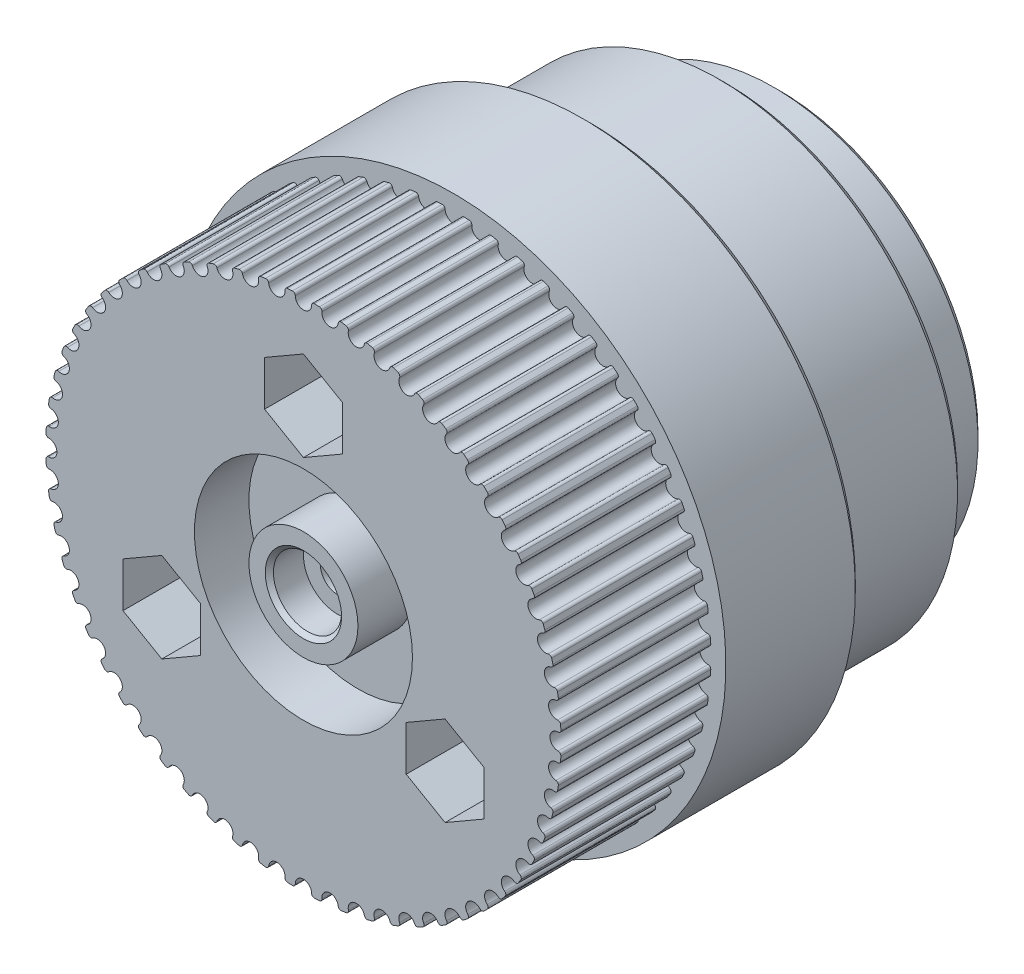
SolidWorks part; units mm, degrees
ref_plane "Front Plane" through (0, 0, 0) normal (0, 0, 1) x (1, 0, 0)
ref_plane "Top Plane" through (0, 0, 0) normal (0, 1, 0) x (1, 0, 0)
ref_plane "Right Plane" through (0, 0, 0) normal (1, 0, 0) x (0, 0, -1)
ref_axis "Axis1" through (0, 0, 55) along (0, 0, -1)
sketch "SketchRevolveGearBelt02" plane through (0, 0, 0) normal (1, 0, 0) x (0, 0, -1)
  line L0 (0, 0) -> (1, 0) construction
  line L1 (11, 0) -> (11, 18.9081)
  line L2 (11, 18.9081) -> (0, 18.9081)
  line L3 (0, 18.9081) -> (0, 0)
  line L4 (0, 0) -> (11, 0)
  dimension "GearBeltSide1" = 11
  dimension "GearBeltOutsideDiameter" = 18.9081
revolve "GearBelt02" add sketch "SketchRevolveGearBelt02" angle 360 about L0
sketch "SketchToothGearBelt02" plane through (0, 0, 0) normal (0, 0, 1) x (1, 0, 0)
  line L0 (-0.8105, 18.8907) -> (0, 21.4481)
  line L1 (0, 21.4481) -> (0.8105, 18.8907)
  arc A0 (0.8105, 18.8907) -> (0.6, 18.6891) centre (0.8018, 18.6891) ccw
  arc A1 (0.6, 18.6891) -> (-0.6, 18.6891) centre (0, 18.6891) cw
  arc A2 (-0.6, 18.6891) -> (-0.8105, 18.8907) centre (-0.8018, 18.6891) ccw
  dimension "GearBeltToothR1" = 0.4036
  dimension "GearBeltToothR2" = 1.2
  dimension "GearBeltToothCapX1" = 0.8105
  dimension "GearBeltToothCapY1" = 2.5574
  dimension "GearBeltToothCapX2" = 0.8105
  dimension "GearBeltToothCapY2" = 2.5574
extrude "ToothExtrudeCutGearBelt02" cut sketch "SketchToothGearBelt02" against normal blind 11
pattern_circular "PatternGearBelt02" count 60 every 6 about axis through (0, 0, 55) along (0, 0, -1) of "ToothExtrudeCutGearBelt02"
sketch "Эскиз2" plane through (0, 0, -11) normal (0, 0, -1) x (-1, 0, 0)
  circle A0 centre (0, 0) radius 20
extrude "Бобышка-Вытянуть1" add sketch "Эскиз2" along normal blind 10
sketch "Эскиз3" plane through (0, 0, -21) normal (0, 0, -1) x (-1, 0, 0)
  circle A0 centre (0, 0) radius 17.5
extrude "Бобышка-Вытянуть2" add sketch "Эскиз3" along normal blind 10
sketch "Эскиз4" plane through (0, 0, -31) normal (0, 0, -1) x (-1, 0, 0)
  circle A0 centre (0, 0) radius 15
extrude "Бобышка-Вытянуть3" add sketch "Эскиз4" along normal blind 4
sketch "Эскиз5" plane through (0, 0, 0) normal (0, 0, 1) x (1, 0, 0)
  circle A0 centre (0, 0) radius 12 construction
  circle A1 centre (0, 12) radius 1.75
  circle A2 centre (10.3923, -6) radius 1.75
  circle A3 centre (-10.3923, -6) radius 1.75
  point P12 (0, 0)
  dimension "D1" = 3.5
  dimension "D2" = 24
  dimension "D3" = 3
extrude "Вырез-Вытянуть1" cut sketch "Эскиз5" against normal through all
sketch "Эскиз6" plane through (0, 0, 0) normal (0, 0, 1) x (1, 0, 0)
  line L1 (0, 8.7091) -> (2.85, 10.3546)
  line L2 (2.85, 10.3546) -> (2.85, 13.6454)
  line L3 (2.85, 13.6454) -> (0, 15.2909)
  line L4 (0, 15.2909) -> (-2.85, 13.6454)
  line L5 (-2.85, 13.6454) -> (-2.85, 10.3546)
  line L6 (-2.85, 10.3546) -> (0, 8.7091)
  circle A0 centre (0, 12) radius 2.85 construction
  dimension "D1" = 5.7
extrude "Вырез-Вытянуть2" cut sketch "Эскиз6" against normal blind 20
pattern_circular "Круговой массив1" count 3 over 360 about axis through (0, 0, -21) along (0, 0, 1) of "Вырез-Вытянуть2" reverse direction yes
chamfer "Chamfer1" distance 0.5 angle 45 3 edges at (-20, 0, -21) (-15, 0, -35) (-17.5, 0, -31)
sketch "Эскиз7" plane through (0, 0, 0) normal (0, 0, 1) x (1, 0, 0)
  circle A0 centre (0, 0) radius 2.5
extrude "Вырез-Вытянуть3" cut sketch "Эскиз7" against normal blind 2.5
chamfer "Фаска1" distance 0.3 angle 45 1 edges at (2.5, 0, 0)
sketch "Эскиз8" plane through (0, 0, 0) normal (0, 0, 1) x (1, 0, 0)
  circle A0 centre (0, 0) radius 1.25
extrude "Вырез-Вытянуть4" cut sketch "Эскиз8" against normal through all both and the other way through all
sketch "Эскиз10" plane through (0, 0, 0) normal (0, 0, 1) x (1, 0, 0)
  circle A0 centre (0, 0) radius 6 construction
  circle A1 centre (0, 0) radius 4
  circle A2 centre (0, 0) radius 8
extrude "Вырез-Вытянуть5" cut sketch "Эскиз10" against normal blind 4
